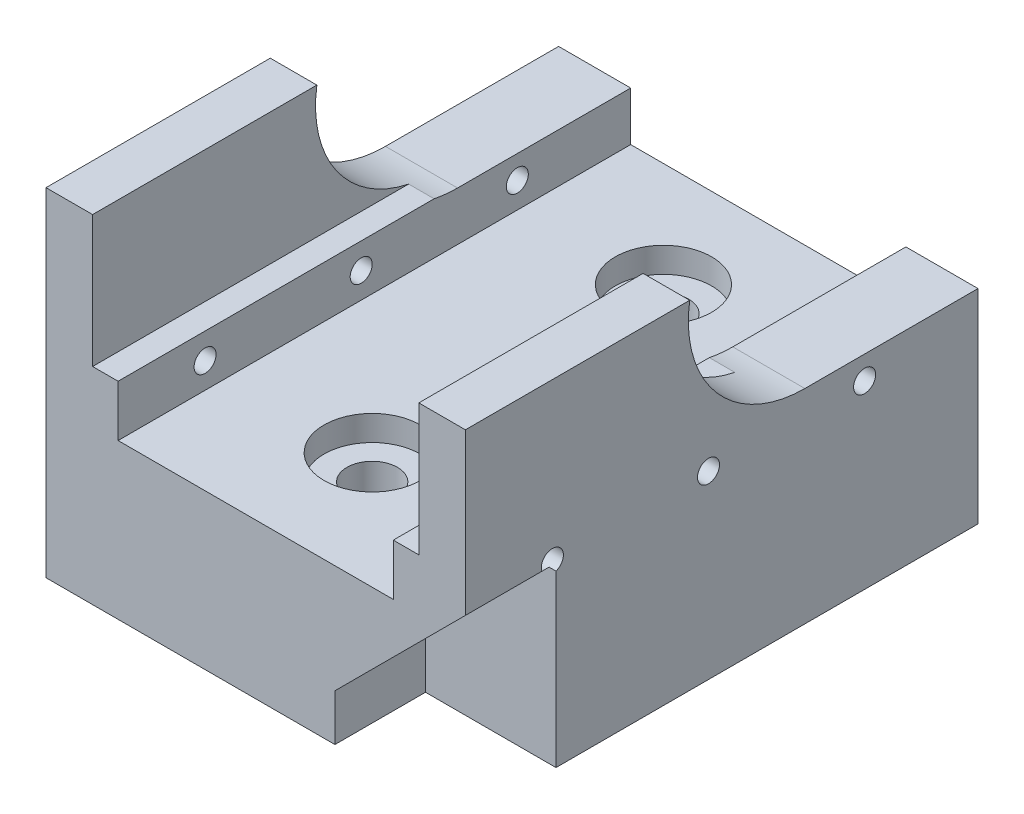
SolidWorks part; units mm, degrees
material "PLA"
ref_plane "Front Plane" through (0, 0, 0) normal (0, 0, 1) x (1, 0, 0)
ref_plane "Top Plane" through (0, 0, 0) normal (0, 1, 0) x (1, 0, 0)
ref_plane "Right Plane" through (0, 0, 0) normal (1, 0, 0) x (0, 0, -1)
sketch "Sketch1" plane through (0, 0, 0) normal (0, 1, 0) x (1, 0, 0)
  line L0 (-22.86, 30.48) -> (22.86, 30.48)
  line L6 (-22.86, 30.48) -> (-22.86, -30.48)
  line L8 (22.86, 30.48) -> (22.86, -30.48)
  line L9 (-22.86, -30.48) -> (22.86, -30.48)
  point P1 (-22.86, 0)
  point P7 (22.86, 0)
  dimension "D3" = 30.48
  dimension "D2" = 45.72
  dimension "D1" = 60.96
  dimension "D4" = 22.86
extrude "Boss-Extrude1" add sketch "Sketch1" along normal blind 6.35
sketch "Sketch2" plane through (0, 6.35, 0) normal (0, 1, 0) x (1, 0, 0)
  line L9 (-22.86, -30.48) -> (22.86, -30.48) construction
  line L10 (-22.86, 30.48) -> (-15, 30.48)
  line L11 (-22.86, 30.48) -> (-22.86, -30.48)
  line L12 (-22.86, -30.48) -> (-15, -30.48)
  line L13 (-15, 30.48) -> (-15, -30.48)
  line L14 (22.86, 30.48) -> (-22.86, 30.48) construction
  line L15 (15, 30.48) -> (22.86, 30.48)
  line L16 (15, 30.48) -> (15, -30.48)
  line L17 (15, -30.48) -> (22.86, -30.48)
  line L18 (22.86, 30.48) -> (22.86, -30.48)
  dimension "D1" = 7.86
  dimension "D2" = 7.86
extrude "Boss-Extrude2" add sketch "Sketch2" along normal blind 20.955
hole_wizard "M2 Clearance Hole2" positions "Sketch6" profile "Sketch7" hole size "M2" standard "ANSI Metric"
sketch "Sketch6" plane through (22.86, 0, 0) normal (1, 0, 0) x (0, 0, -1)
  line L0 (-30.48, 27.305) -> (-30.48, 0) construction
  line L1 (-30.48, 0) -> (30.48, 0) construction
  point P0 (-15.9172, 10.16)
  dimension "D1" = 14.5628
  dimension "D2" = 10.16
sketch "Sketch7" plane through (22.86, 10.16, 15.9172) normal (0, 1, 0) x (0, 0, -1)
  line L0 (0, 0) -> (0, 46.441)
  line L1 (0, 46.441) -> (1.2, 45.72)
  line L2 (1.2, 45.72) -> (1.2, 0)
  line L5 (1.2, 0) -> (0, 0)
  line L10 (0, 46.441) -> (-1.2, 45.72) construction
  line L11 (0, -6.35) -> (0, 107.95) construction
  dimension "Hole Dia." = 2.4
  dimension "Hole Depth" = 45.72
  dimension "Drill Angle" = 118
pattern_linear "LPattern1" count 3 spacing 17.018 along (0, 0, -1) of "M2 Clearance Hole2"
extrude "Boss-Extrude3" add sketch "Sketch1<3>" against normal blind 2.54
sketch "Sketch1<3>" plane through (0, 0, 0) normal (0, 1, 0) x (1, 0, 0) same geometry as "Sketch1"
sketch "Sketch8" plane through (-22.86, 0, 0) normal (-1, 0, 0) x (0, 0, 1)
  line L0 (-30.48, 27.305) -> (-30.48, -2.54) construction
  line L1 (-30.48, -2.54) -> (-14.605, -2.54)
  line L2 (-30.48, -2.54) -> (-30.48, 3.81)
  line L3 (-30.48, 3.81) -> (-14.605, 3.81)
  line L4 (-14.605, -2.54) -> (-14.605, 3.81)
  line L5 (-30.48, -2.54) -> (30.48, -2.54) construction
  dimension "D1" = 15.875
  dimension "D2" = 6.35
sketch "Sketch11" plane through (15, 0, 0) normal (-1, 0, 0) x (0, 0, 1)
  line L0 (30.48, 27.305) -> (30.48, 6.35) construction
  line L1 (-30.48, 27.305) -> (30.48, 27.305)
  line L2 (-30.48, 27.305) -> (-30.48, 12.96)
  line L3 (-30.48, 12.96) -> (30.48, 12.96)
  line L4 (30.48, 27.305) -> (30.48, 12.96)
  dimension "D1" = 14.345
extrude "Cut-Extrude1" cut sketch "Sketch11" against normal mid plane 35.56 from surface starting at plane "Right Plane"
sketch "Sketch12" plane through (22.86, 0, 0) normal (1, 0, 0) x (0, 0, -1)
  line L0 (30.48, 27.305) -> (30.48, -2.54) construction
  line L1 (11.605, 12.7) -> (30.48, 12.7)
  line L2 (30.48, 12.7) -> (30.48, 27.305)
  line L3 (30.48, 27.305) -> (24.1613, 27.305)
  line L5 (-30.48, 27.305) -> (30.48, 27.305) construction
  arc A0 (24.1613, 27.305) -> (11.605, 12.7) centre (11.605, 25.4) ccw
  dimension "D3" = 25.4
  dimension "D1" = 18.875
  dimension "D2" = 1.905
extrude "Cut-Extrude2" cut sketch "Sketch12" against normal through all
fillet "Fillet3" [suppressed] radius 0.762
sketch "Sketch17" plane through (0, -2.54, 0) normal (0, -1, 0) x (1, 0, 0)
  line L0 (-22.86, 30.48) -> (22.86, 30.48) construction
  line L1 (-22.86, 30.48) -> (22.86, 30.48)
  line L2 (-22.86, 30.48) -> (-22.86, -30.48)
  line L3 (-22.86, -30.48) -> (22.86, -30.48)
  line L4 (22.86, 30.48) -> (22.86, -30.48)
  line L5 (22.86, -30.48) -> (-22.86, -30.48) construction
  line L6 (22.86, 30.48) -> (22.86, -30.48) construction
  line L7 (-22.86, -30.48) -> (-22.86, 30.48) construction
extrude "Boss-Extrude4" add sketch "Sketch17" along normal blind 6.985
fillet "Fillet5" [suppressed] radius 0.762
sketch "Sketch19" plane through (0, 6.35, 0) normal (0, 1, 0) x (1, 0, 0)
  line L0 (15, 30.48) -> (15, -30.48) construction
  line L1 (-15, -30.48) -> (15, -30.48)
  line L2 (-15, -30.48) -> (-15, 30.48)
  line L3 (-15, 30.48) -> (15, 30.48)
  line L4 (15, -30.48) -> (15, 30.48)
  line L5 (15, 30.48) -> (-15, 30.48) construction
extrude "Boss-Extrude5" add sketch "Sketch19" along normal blind 1.01
hole_wizard "CBORE for M5 SBHCS2" positions "Sketch20" profile "Sketch21" counterbore size "M5" standard "ANSI Metric" end condition through all
sketch "Sketch20" plane through (0, 7.36, 0) normal (0, 1, 0) x (1, 0, 0)
  point P2 (0, -12.7)
  point P5 (0, 19.05)
  dimension "D1" = 31.75
  dimension "D2" = 12.7
sketch "Sketch21" plane through (0, 7.36, 12.7) normal (1, 0, 0) x (0, 0, 1)
  line L0 (0, 0) -> (0, 16.885)
  line L1 (0, 16.885) -> (2.75, 16.885)
  line L3 (2.75, 16.885) -> (2.75, 2.75)
  line L4 (2.75, 2.75) -> (5.25, 2.75)
  line L5 (5.25, 2.75) -> (5.25, 0)
  line L7 (5.25, 0) -> (0, 0)
  line L11 (0, -6.35) -> (0, 107.95) construction
  dimension "Thru Hole Dia." = 5.5
  dimension "Thru Hole Depth" = 16.885
  dimension "C'Bore Dia." = 10.5
  dimension "C'Bore Depth" = 2.75
fillet "Fillet6" [suppressed] radius 0.762
sketch "Sketch24" plane through (31.5712, -12.7, -14.6188) normal (0, 1, 0) x (0, 0, -1)
  line L0 (-45.0988, 8.7112) -> (-15.5701, 8.7112) construction
  line L1 (-45.0988, 54.4312) -> (-40.0188, 54.4312)
  line L2 (-45.0988, 54.4312) -> (-45.0988, 8.7112)
  line L3 (-45.0988, 8.7112) -> (-40.0188, 8.7112)
  line L4 (-40.0188, 54.4312) -> (-40.0188, 8.7112)
  dimension "D1" = 5.08
extrude "Cut-Extrude3" cut sketch "Sketch24" against normal through all both and the other way through all
sketch "Sketch25" plane through (0, 0, 25.4) normal (0, 0, 1) x (1, 0, 0)
  line L0 (8.636, -9.525) -> (8.636, -4.445)
  line L1 (22.86, -9.525) -> (-22.86, -9.525) construction
  line L2 (8.636, -4.445) -> (22.86, 9.779)
  line L3 (22.86, 27.305) -> (22.86, -9.525) construction
  line L4 (8.636, -9.525) -> (22.86, -9.525)
  line L5 (22.86, -9.525) -> (22.86, 9.779)
  dimension "D1" = 5.08
  dimension "D2" = 135
  dimension "D3" = 14.224
extrude "Cut-Extrude4" cut sketch "Sketch25" against normal blind 9.874
